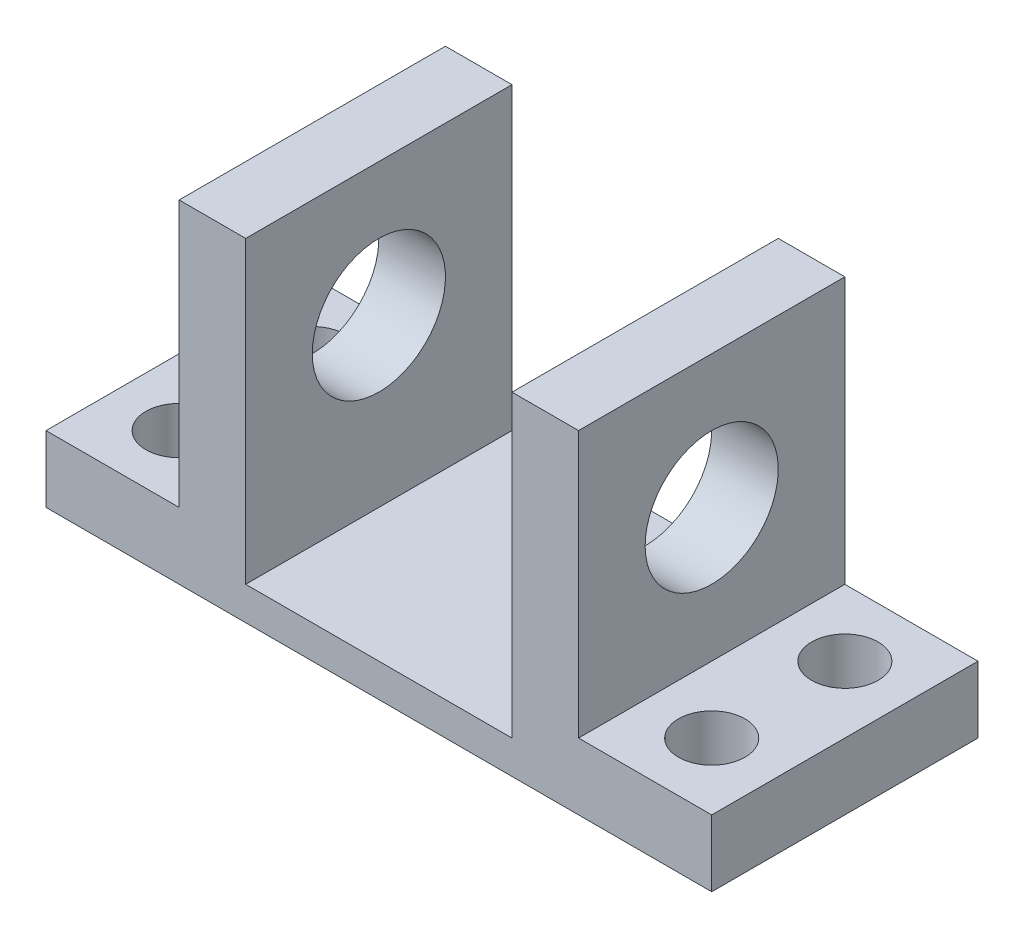
SolidWorks part; units mm, degrees
ref_plane "Front Plane" through (0, 0, 0) normal (0, 0, 1) x (1, 0, 0)
ref_plane "Top Plane" through (0, 0, 0) normal (0, 1, 0) x (1, 0, 0)
ref_plane "Right Plane" through (0, 0, 0) normal (1, 0, 0) x (0, 0, -1)
sketch "Sketch2" plane through (0, 0, 0) normal (0, 1, 0) x (1, 0, 0)
  line L0 (6.35, 0) -> (6.35, 25.4)
  line L1 (0, 0) -> (38.1, 0)
  line L2 (0, 0) -> (0, 25.4)
  line L3 (0, 25.4) -> (38.1, 25.4)
  line L4 (38.1, 0) -> (38.1, 25.4)
  line L5 (31.75, 0) -> (31.75, 25.4)
  dimension "D1" = 38.1
  dimension "D2" = 25.4
  dimension "D3" = 6.35
  dimension "D4" = 6.35
extrude "Boss-Extrude1" add sketch "Sketch2" along normal blind 31.75 contours L3 L2 L1 L0 | L5 L1 L4 L3 region at (3.175, 0, -12.7) region at (34.925, 0, -12.7)
extrude "Boss-Extrude2" add sketch "Sketch2<3>" along normal blind 3.175 contours L1 L5 L3 L0 region at (19.05, 0, -12.7)
sketch "Sketch2<3>" plane through (0, 0, 0) normal (0, 1, 0) x (1, 0, 0) same geometry as "Sketch2"
sketch "Sketch3" plane through (0, 0, 0) normal (-1, 0, 0) x (0, 0, 1)
  line L0 (-12.7, 31.75) -> (-12.7, 19.05) construction
  line L1 (0, 31.75) -> (-25.4, 31.75) construction
  circle A0 centre (-12.7, 19.05) radius 6.35
  dimension "D2" = 12.7
  dimension "D1" = 12.7
extrude "Cut-Extrude1" cut sketch "Sketch3" against normal through all
sketch "Sketch4" plane through (0, 0, 0) normal (-1, 0, 0) x (0, 0, 1)
  line L0 (0, 31.75) -> (0, 0) construction
  line L1 (-25.4, 0) -> (0, 0)
  line L2 (-25.4, 0) -> (-25.4, 6.35)
  line L3 (-25.4, 6.35) -> (0, 6.35)
  line L4 (0, 0) -> (0, 6.35)
  dimension "D1" = 6.35
extrude "Boss-Extrude3" add sketch "Sketch4" along normal blind 12.7
sketch "Sketch9" plane through (38.1, 0, 0) normal (1, 0, 0) x (0, 0, -1)
  line L0 (25.4, 31.75) -> (25.4, 0) construction
  line L1 (0, 0) -> (25.4, 0)
  line L2 (0, 0) -> (0, 6.35)
  line L3 (0, 6.35) -> (25.4, 6.35)
  line L4 (25.4, 0) -> (25.4, 6.35)
  dimension "D1" = 6.35
extrude "Boss-Extrude5" add sketch "Sketch9" along normal blind 12.7
sketch "Sketch10" plane through (0, 6.35, 0) normal (0, 1, 0) x (1, 0, 0)
  line L0 (-12.7, 19.05) -> (50.8, 19.05) construction
  line L1 (-12.7, 0) -> (-12.7, 25.4) construction
  line L2 (50.8, 25.4) -> (50.8, 0) construction
  line L3 (-12.7, 6.35) -> (50.8, 6.35) construction
  line L4 (-12.7, 0) -> (0, 0) construction
  line L5 (-12.7, 25.4) -> (0, 25.4) construction
  dimension "D1" = 6.35
  dimension "D2" = 6.35
hole_wizard "1/4 (0.25) Diameter Hole1" positions "3DSketch3" profile "Sketch11" hole size "1/4" standard "ANSI Inch"
sketch3d "3DSketch3"
  line L0 (-12.7, 6.35, -19.05) -> (50.8, 6.35, -19.05) construction
  line L1 (-12.7, 6.35, -6.35) -> (50.8, 6.35, -6.35) construction
  point P0 (-6.35, 6.35, -19.05)
  point P4 (-6.35, 6.35, -6.35)
  point P8 (44.45, 6.35, -6.35)
  point P10 (44.45, 6.35, -19.05)
  dimension "D1" = 6.35
  dimension "D2" = 6.35
  dimension "D3" = 6.35
  dimension "D4" = 6.35
sketch "Sketch11" plane through (-6.35, 6.35, -19.05) normal (1, 0, 0) x (0, 0, 1)
  line L0 (0, 0) -> (0, 27.3077)
  line L1 (0, 27.3077) -> (3.175, 25.4)
  line L2 (3.175, 25.4) -> (3.175, 0)
  line L5 (3.175, 0) -> (0, 0)
  line L10 (0, 27.3077) -> (-3.175, 25.4) construction
  line L11 (0, -6.35) -> (0, 107.95) construction
  dimension "Hole Dia." = 6.35
  dimension "Hole Depth" = 25.4
  dimension "Drill Angle" = 118
